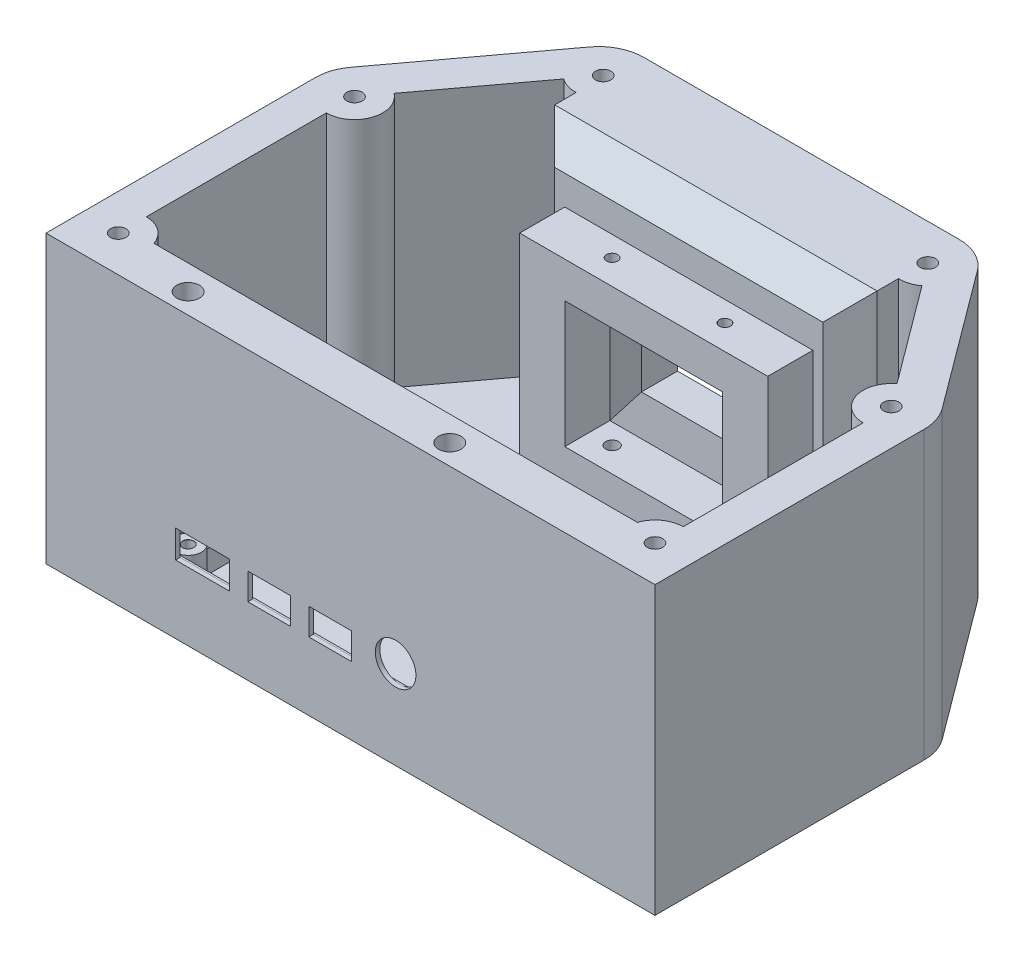
SolidWorks part; units mm, degrees
ref_plane "Front Plane" through (0, 0, 0) normal (0, 0, 1) x (1, 0, 0)
ref_plane "Top Plane" through (0, 0, 0) normal (0, 1, 0) x (1, 0, 0)
ref_plane "Right Plane" through (0, 0, 0) normal (1, 0, 0) x (0, 0, -1)
sketch "Sketch1" plane through (0, 0, 0) normal (0, 1, 0) x (1, 0, 0)
  line L0 (-112.8099, -62.3676) -> (-112.8099, -13.3676) construction
  line L1 (-112.8099, -13.3676) -> (-54.8099, -13.3676) construction
  line L2 (-54.8099, -13.3676) -> (-54.8099, -62.3676) construction
  line L3 (-54.8099, -62.3676) -> (-112.8099, -62.3676) construction
  line L4 (-139.8099, -3.8676) -> (-112.3099, 33.1324)
  line L5 (-139.8099, -66.8676) -> (-4.8099, -66.8676)
  line L8 (-4.8099, -66.8676) -> (-4.8099, -3.8676)
  line L9 (-72.3099, 46.1894) -> (-72.3099, -66.8676) construction
  line L10 (-4.8099, -3.8676) -> (-32.3099, 33.1324)
  line L11 (-32.3099, 33.1324) -> (-112.3099, 33.1324)
  line L12 (-139.8099, -3.8676) -> (-139.8099, -66.8676)
  dimension "D1" = 49
  dimension "D2" = 58
  dimension "D3" = 135
  dimension "D4" = 100
  dimension "D5" = 50
  dimension "D6" = 4.5
  dimension "D7" = 80
  dimension "D9" = 63
extrude "Boss-Extrude1" add sketch "Sketch1" along normal blind 7
sketch "Sketch2" plane through (0, 7, 0) normal (0, 1, 0) x (1, 0, 0)
  line L0 (-72.3099, 33.1324) -> (-72.3099, -66.8676) construction
  line L1 (-32.3099, 33.1324) -> (-112.3099, 33.1324) construction
  line L2 (-139.8099, -66.8676) -> (-4.8099, -66.8676) construction
  line L3 (-4.8099, -66.8676) -> (-4.8099, -3.8676) construction
  line L5 (-112.8099, -13.3676) -> (-54.8099, -13.3676) construction
  line L6 (-54.8099, -62.3676) -> (-112.8099, -62.3676) construction
  line L7 (-112.8099, -62.3676) -> (-112.8099, -13.3676) construction
  line L8 (-54.8099, -13.3676) -> (-54.8099, -62.3676) construction
  line L9 (-83.8099, -62.3676) -> (-83.8099, -13.3676) construction
  line L10 (-112.8099, -37.8676) -> (-54.8099, -37.8676) construction
  line L11 (-112.8099, -65.3676) -> (-54.8099, -65.3676)
  line L12 (-115.8099, -62.3676) -> (-115.8099, -13.3676)
  line L13 (-112.8099, -10.3676) -> (-54.8099, -10.3676)
  line L14 (-51.8099, -13.3676) -> (-51.8099, -62.3676)
  line L15 (-112.8099, -16.3676) -> (-112.8099, -59.3676)
  line L16 (-109.8099, -62.3676) -> (-57.8099, -62.3676)
  line L17 (-54.8099, -16.3676) -> (-54.8099, -59.3676)
  line L18 (-109.8099, -13.3676) -> (-57.8099, -13.3676)
  line L22 (-99.8099, -1.8676) -> (-44.8099, -1.8676)
  line L23 (-99.8099, -1.8676) -> (-99.8099, 8.1324)
  line L24 (-99.8099, 8.1324) -> (-44.8099, 8.1324)
  line L25 (-44.8099, -1.8676) -> (-44.8099, 8.1324)
  line L26 (-99.8099, -1.8676) -> (-44.8099, 8.1324) construction
  line L27 (-99.8099, 8.1324) -> (-44.8099, -1.8676) construction
  circle A0 centre (-112.8099, -13.3676) radius 3
  circle A1 centre (-112.8099, -62.3676) radius 3
  circle A2 centre (-54.8099, -62.3676) radius 3
  circle A3 centre (-54.8099, -13.3676) radius 3
  point P42 (-72.3099, 3.1324)
  dimension "D6" = 6
  dimension "D1" = 55
  dimension "D2" = 50
  dimension "D3" = 4.5
  dimension "D4" = 58
  dimension "D5" = 49
  dimension "D7" = 10
  dimension "D8" = 35
extrude "Boss-Extrude2" add sketch "Sketch2" along normal blind 5 contours L12 A1 L15 A0 | L18 A3 L13 A0 | A2 L16 A1 L11 | L14 A3 L17 A2 region at (-83.8099, 7, 63.8877) region at (-114.334, 7, 37.8676) region at (-53.2858, 7, 37.8676) region at (-83.8099, 7, 11.8476)
extrude "Boss-Extrude3" add sketch "Sketch2<3>" along normal blind 8 contours A0 | A3 | A2 | A1 region at (-112.8099, 7, 62.3676) region at (-54.8099, 7, 62.3676) region at (-112.8099, 7, 13.3676) region at (-54.8099, 7, 13.3676)
sketch "Sketch2<3>" plane through (0, 7, 0) normal (0, 1, 0) x (1, 0, 0) same geometry as "Sketch2"
hole_wizard "Ø2.5mm Dowel Hole1" positions "Sketch4" profile "Sketch6" hole size "Ø2.5" standard "ANSI Metric"
sketch "Sketch4" plane through (0, 15, 0) normal (0, 1, 0) x (1, 0, 0)
  point P0 (-54.8099, -13.3676)
  point P3 (-112.8099, -13.3676)
  point P6 (-54.8099, -62.3676)
  point P12 (-112.8099, -62.3676)
sketch "Sketch6" plane through (-54.8099, 15, 13.3676) normal (1, 0, 0) x (0, 0, 1)
  line L0 (0, 0) -> (0, 8.7511)
  line L1 (0, 8.7511) -> (1.25, 8)
  line L2 (1.25, 8) -> (1.25, 0.025)
  line L3 (1.25, 0.025) -> (1.275, 0)
  line L5 (1.275, 0) -> (0, 0)
  line L6 (-1.25, 0.025) -> (-1.275, 0) construction
  line L10 (0, 8.7511) -> (-1.25, 8) construction
  line L11 (0, -6.35) -> (0, 107.95) construction
  dimension "Hole Dia." = 2.5
  dimension "Hole Depth" = 8
  dimension "Near C'Sink Dia." = 2.55
  dimension "Near C'Sink Angle" = 90
  dimension "Drill Angle" = 118
extrude "Boss-Extrude4" add sketch "Sketch2<4>" along normal blind 8 contours L22 L25 L24 L23 region at (-72.3099, 7, -3.1324)
sketch "Sketch2<4>" plane through (0, 7, 0) normal (0, 1, 0) x (1, 0, 0) same geometry as "Sketch2"
sketch "Sketch7" plane through (0, 15, 0) normal (0, 1, 0) x (1, 0, 0)
  line L0 (-99.8099, -1.8676) -> (-44.8099, -1.8676) construction
  line L1 (-99.8099, 8.1324) -> (-89.8099, 8.1324)
  line L2 (-99.8099, 8.1324) -> (-99.8099, -1.8676)
  line L3 (-99.8099, -1.8676) -> (-89.8099, -1.8676)
  line L4 (-89.8099, 8.1324) -> (-89.8099, -1.8676)
  line L5 (-72.3099, 8.1324) -> (-72.3099, -1.8676) construction
  line L10 (-99.8099, 8.1324) -> (-44.8099, 8.1324) construction
  line L11 (-44.8099, -1.8676) -> (-54.8099, -1.8676)
  line L12 (-54.8099, 8.1324) -> (-54.8099, -1.8676)
  line L13 (-44.8099, 8.1324) -> (-54.8099, 8.1324)
  line L14 (-44.8099, 8.1324) -> (-44.8099, -1.8676)
  dimension "D1" = 10
extrude "Boss-Extrude5" add sketch "Sketch7" along normal blind 28
sketch "Sketch9" plane through (0, 43, 0) normal (0, 1, 0) x (1, 0, 0)
  line L1 (-99.8099, 8.1324) -> (-44.8099, 8.1324)
  line L2 (-99.8099, 8.1324) -> (-99.8099, -1.8676)
  line L3 (-99.8099, -1.8676) -> (-44.8099, -1.8676)
  line L4 (-44.8099, 8.1324) -> (-44.8099, -1.8676)
extrude "Boss-Extrude6" add sketch "Sketch9" along normal blind 8
sketch "Sketch10" plane through (0, 0, -33.1324) normal (0, 0, -1) x (-1, 0, 0)
  line L0 (72.3099, 7) -> (72.3099, 51) construction
  line L1 (32.3099, 7) -> (44.8099, 7)
  line L2 (32.3099, 7) -> (32.3099, 51)
  line L3 (32.3099, 51) -> (44.8099, 51)
  line L4 (44.8099, 7) -> (44.8099, 51)
  line L5 (32.3099, 7) -> (112.3099, 7) construction
  line L6 (44.8099, 51) -> (99.8099, 51) construction
  line L7 (112.3099, 51) -> (99.8099, 51)
  line L8 (99.8099, 7) -> (99.8099, 51)
  line L9 (112.3099, 7) -> (99.8099, 7)
  line L10 (112.3099, 7) -> (112.3099, 51)
  line L11 (44.8099, 7) -> (99.8099, 7)
  line L12 (32.3099, 51) -> (112.3099, 51)
  line L13 (32.3099, 51) -> (32.3099, 63.5)
  line L14 (32.3099, 63.5) -> (112.3099, 63.5)
  line L15 (112.3099, 51) -> (112.3099, 63.5)
  line L16 (44.8099, 51) -> (99.8099, 51)
  line L17 (44.8099, 51) -> (99.8099, 51)
  line M16 (112.3099, 7) -> (32.3099, 7)
  dimension "D1" = 12.5
extrude "Boss-Extrude7" add sketch "Sketch10" against normal blind 8 contours L4 L3 L2 M16 | L7 L15 L14 L13 L3 L12 L17 | L10 L7 L8 M16 region at (-38.5599, 29, -33.1324) region at (-72.3099, 57.25, -33.1324) region at (-106.0599, 29, -33.1324)
sketch "Sketch11" plane through (0, 7, 0) normal (0, 1, 0) x (1, 0, 0)
  line L0 (-44.8099, 25.1324) -> (-99.8099, 25.1324)
  line L1 (-131.8099, -66.8676) -> (-131.8099, -6.515)
  line L2 (-139.8099, -66.8676) -> (-4.8099, -66.8676) construction
  line L3 (-131.8099, -6.515) -> (-108.2882, 25.1324)
  line L9 (-32.3099, 25.1324) -> (-112.3099, 25.1324) construction
  line L13 (-32.3099, 33.1324) -> (-112.3099, 33.1324) construction
  line L15 (-112.3099, 33.1324) -> (-139.8099, -3.8676) construction
  line L16 (-108.2882, 25.1324) -> (-108.2882, 33.1324)
  line L17 (-108.2882, 33.1324) -> (-112.3099, 33.1324)
  line L18 (-112.3099, 33.1324) -> (-139.8099, -3.8676)
  line L19 (-139.8099, -3.8676) -> (-139.8099, -66.8676)
  line L20 (-139.8099, -66.8676) -> (-131.8099, -66.8676)
  line L21 (-72.3099, 33.1324) -> (-72.3099, -66.8676) construction
  line L22 (-4.8099, -66.8676) -> (-12.8099, -66.8676)
  line L23 (-4.8099, -3.8676) -> (-4.8099, -66.8676)
  line L24 (-32.3099, 33.1324) -> (-4.8099, -3.8676)
  line L25 (-36.3316, 33.1324) -> (-32.3099, 33.1324)
  line L26 (-36.3316, 25.1324) -> (-36.3316, 33.1324)
  line L27 (-12.8099, -6.515) -> (-36.3316, 25.1324)
  line L28 (-12.8099, -66.8676) -> (-12.8099, -6.515)
  line L29 (-51.8099, -58.8676) -> (-12.8099, -58.8676)
  line L30 (-51.8099, -13.3676) -> (-51.8099, -62.3676) construction
  line L31 (-115.8099, -58.8676) -> (-131.8099, -58.8676)
  line L32 (-115.8099, -62.3676) -> (-115.8099, -13.3676) construction
  line L33 (-131.8099, -65.3676) -> (-12.8099, -65.3676)
  line M19 (-99.8099, 25.1324) -> (-112.3099, 25.1324)
  line M20 (-112.3099, 25.1324) -> (-112.3099, 33.1324)
  line M21 (-112.3099, 33.1324) -> (-139.8099, -3.8676)
  line M22 (-139.8099, -3.8676) -> (-139.8099, -66.8676)
  line M23 (-139.8099, -66.8676) -> (-4.8099, -66.8676)
  dimension "D1" = 8
  dimension "D2" = 8
  dimension "D3" = 8
  dimension "D4" = 8
  dimension "D5" = 8
  dimension "D6" = 8
  dimension "D7" = 119
  dimension "D8" = 16
  dimension "D9" = 1.5
extrude "Boss-Extrude10" add sketch "Sketch11" along normal blind 56.5 contours L1 L3 M19 M20 M21 M22 M23 | L22 L28 L27 L26 L25 L24 L23 region at (-135.8099, 7, 65.8191)
fillet "Fillet8" radius 10 4 edges at (-139.8099, 31.75, 3.8676) (-112.3099, 31.75, -33.1324) (-4.8099, 31.75, 3.8676) (-32.3099, 31.75, -33.1324)
sketch "Sketch16" plane through (0, 0, 66.8676) normal (0, 0, 1) x (1, 0, 0)
  line L0 (-73.5599, 19.04) -> (-73.5599, 17.7198) construction
  line L1 (-111.0799, 21.25) -> (-99.1399, 21.25)
  line L2 (-111.0799, 21.25) -> (-111.0799, 15.09)
  line L3 (-111.0799, 15.09) -> (-99.1399, 15.09)
  line L4 (-99.1399, 21.25) -> (-99.1399, 15.09)
  line L5 (-95.0599, 20.99) -> (-85.5599, 20.99)
  line L6 (-95.0599, 20.99) -> (-95.0599, 15.09)
  line L7 (-95.0599, 15.09) -> (-85.5599, 15.09)
  line L8 (-85.5599, 20.99) -> (-85.5599, 15.09)
  line L9 (-81.5599, 20.99) -> (-72.0599, 20.99)
  line L10 (-81.5599, 20.99) -> (-81.5599, 15.09)
  line L11 (-81.5599, 15.09) -> (-72.0599, 15.09)
  line L12 (-72.0599, 20.99) -> (-72.0599, 15.09)
  line L13 (-80.0599, 17.7198) -> (-80.0599, 19.04) construction
  line L14 (-76.9699, 16.59) -> (-78.9654, 16.59) construction
  line L15 (-79.6099, 19.49) -> (-74.0099, 19.49) construction
  line L16 (-93.1099, 19.49) -> (-87.5099, 19.49) construction
  line L17 (-90.4699, 16.59) -> (-92.4654, 16.59) construction
  line L18 (-93.5599, 17.7198) -> (-93.5599, 19.04) construction
  line L19 (-87.0599, 19.04) -> (-87.0599, 17.7198) construction
  line L20 (-108.2799, 19.75) -> (-101.9399, 19.75) construction
  line L21 (-108.2799, 16.59) -> (-101.9399, 16.59) construction
  line L22 (-109.5799, 17.89) -> (-109.5799, 18.45) construction
  line L23 (-100.6399, 17.89) -> (-100.6399, 18.45) construction
  circle A0 centre (-62.3099, 19.59) radius 4.5
  circle A1 centre (-62.3099, 19.59) radius 3 construction
  dimension "D1" = 1.5
  dimension "D2" = 1.5
  dimension "D3" = 1.5
  dimension "D4" = 1.5
  dimension "D5" = 1.5
  dimension "D6" = 1.5
  dimension "D7" = 1.5
  dimension "D8" = 1.5
  dimension "D9" = 1.5
  dimension "D10" = 1.5
  dimension "D11" = 1.5
  dimension "D12" = 1.5
  dimension "D13" = 1.5
hole_wizard "Ø2.5mm Dowel Hole2" positions "Sketch18" profile "Sketch19" hole size "Ø2.5" standard "ANSI Metric" end condition up to next
sketch "Sketch18" plane through (0, 51, 0) normal (0, 1, 0) x (1, 0, 0)
  point P0 (-84.8099, 3.6324)
  point P3 (-59.8099, 3.6324)
sketch "Sketch19" plane through (-84.8099, 51, -3.6324) normal (1, 0, 0) x (0, 0, 1)
  line L0 (0, 0) -> (0, 8)
  line L1 (0, 8) -> (1.25, 8)
  line L2 (1.25, 8) -> (1.25, 0)
  line L5 (1.25, 0) -> (0, 0)
  line L11 (0, -6.35) -> (0, 107.95) construction
  dimension "Thru Hole Dia." = 2.5
  dimension "Thru Hole Depth" = 8
hole_wizard "CBORE for M2.5 Hex Head Machine Screw1" positions "Sketch20" profile "Sketch23" counterbore size "M2.5" standard "ANSI Metric" end condition up to next
sketch "Sketch20" plane through (0, 0, 0) normal (0, -1, 0) x (-1, 0, 0)
  point P0 (59.8099, 3.6324)
  point P3 (84.8099, 3.6324)
sketch "Sketch23" plane through (-59.8099, 0, -3.6324) normal (1, 0, 0) x (0, 0, -1)
  line L0 (0, 0) -> (0, 15)
  line L1 (0, 15) -> (1.45, 15)
  line L3 (1.45, 15) -> (1.45, 12)
  line L4 (1.45, 12) -> (3.64, 12)
  line L5 (3.64, 12) -> (3.64, 0)
  line L7 (3.64, 0) -> (0, 0)
  line L11 (0, -6.35) -> (0, 107.95) construction
  dimension "Thru Hole Dia." = 2.9
  dimension "Thru Hole Depth" = 15
  dimension "C'Bore Dia." = 7.28
  dimension "C'Bore Depth" = 12
sketch "Sketch26" plane through (0, 7, 0) normal (0, 1, 0) x (1, 0, 0)
  line L0 (-115.8099, -58.8676) -> (-131.8099, -58.8676)
  line L1 (-115.8099, -62.3676) -> (-115.8099, -13.3676) construction
  line L2 (-131.8099, -66.8676) -> (-131.8099, -6.515) construction
  line L3 (-131.8099, -66.8676) -> (-12.8099, -66.8676) construction
  line L4 (-51.8099, -58.8676) -> (-12.8099, -58.8676)
  line L5 (-51.8099, -13.3676) -> (-51.8099, -62.3676) construction
  line L6 (-12.8099, -66.8676) -> (-12.8099, -6.515) construction
  line L7 (-12.8099, -58.8676) -> (-12.8099, -66.8676)
  line L8 (-12.8099, -66.8676) -> (-131.8099, -66.8676)
  line L9 (-131.8099, -66.8676) -> (-131.8099, -58.8676)
  line L11 (-51.8099, -58.8676) -> (-51.8099, -62.3676)
  line L12 (-51.8099, -62.3676) -> (-54.8099, -65.3676)
  line L13 (-54.8099, -65.3676) -> (-112.8099, -65.3676)
  line L14 (-112.8099, -65.3676) -> (-115.8099, -62.3676)
  line L15 (-115.8099, -62.3676) -> (-115.8099, -58.8676)
  circle A2 centre (-112.8099, -62.3676) radius 3 construction
  dimension "D1" = 8
extrude "Boss-Extrude11" add sketch "Sketch26" along normal up to surface (8 mm away) up to face at (-112.8099, 15, 63.6426)
sketch "Sketch27" plane through (0, 15, 0) normal (0, 1, 0) x (1, 0, 0)
  line L0 (-118.3099, -58.8676) -> (-118.3099, -65.8676)
  line L1 (-115.8099, -58.8676) -> (-131.8099, -58.8676) construction
  line L2 (-118.3099, -65.8676) -> (-12.8099, -65.8676)
  line L3 (-12.8099, -66.8676) -> (-12.8099, -58.8676) construction
  line L4 (-116.3099, -12.8676) -> (-116.3099, -62.8676) construction
  line L5 (-131.8099, -66.8676) -> (-12.8099, -66.8676) construction
  line L14 (-54.8099, -65.3676) -> (-112.8099, -65.3676)
  line L15 (-115.8099, -62.3676) -> (-115.8099, -58.8676)
  line L16 (-115.8099, -58.8676) -> (-131.8099, -58.8676)
  line L17 (-131.8099, -58.8676) -> (-131.8099, -66.8676)
  line L18 (-131.8099, -66.8676) -> (-12.8099, -66.8676)
  line L19 (-12.8099, -66.8676) -> (-12.8099, -58.8676)
  line L20 (-12.8099, -58.8676) -> (-51.8099, -58.8676)
  line L21 (-51.8099, -58.8676) -> (-51.8099, -62.3676)
  line L24 (-118.3099, -58.8676) -> (-131.8099, -58.8676)
  line L25 (-131.8099, -58.8676) -> (-131.8099, -66.8676)
  line L26 (-131.8099, -66.8676) -> (-12.8099, -66.8676)
  line L27 (-12.8099, -66.8676) -> (-12.8099, -65.8676)
  arc A2 (-51.8099, -62.3676) -> (-54.8099, -65.3676) centre (-54.8099, -62.3676) ccw
  arc A3 (-112.8099, -65.3676) -> (-115.8099, -62.3676) centre (-112.8099, -62.3676) ccw
  dimension "D1" = 2
  dimension "D2" = 1
  dimension "D3" = 0
extrude "Boss-Extrude12" add sketch "Sketch27" along normal blind 20 contours L24 L25 L26 L27 L2 L0
sketch "Sketch28" plane through (0, 35, 0) normal (0, 1, 0) x (1, 0, 0)
  line L6 (-12.8099, -66.8676) -> (-12.8099, -6.515) construction
  line L7 (-131.8099, -66.8676) -> (-12.8099, -66.8676)
  line L8 (-131.8099, -66.8676) -> (-131.8099, -56.8676)
  line L9 (-131.8099, -56.8676) -> (-12.8099, -56.8676)
  line L10 (-12.8099, -66.8676) -> (-12.8099, -56.8676)
  dimension "D1" = 10
extrude "Boss-Extrude13" add sketch "Sketch28" along normal up to surface (28.5 mm away) up to face at (-72.3099, 63.5, 7.5207)
extrude "Cut-Extrude1" cut sketch "Sketch16" against normal up to next
chamfer "Chamfer1" distance 9 angle 45 1 edges at (-72.3099, 35, 56.8676)
sketch "Sketch29" plane through (0, 63.5, 0) normal (0, 1, 0) x (1, 0, 0)
  circle A0 centre (-112.8099, -62.3676) radius 2.5
  circle A1 centre (-54.8099, -62.3676) radius 2.5
  dimension "D1" = 5
  dimension "D2" = 5
extrude "Cut-Extrude2" cut sketch "Sketch29" against normal up to next
sketch "Sketch30" plane through (0, 0, 0) normal (0, -1, 0) x (1, 0, 0)
  line L0 (-139.8099, 7.1769) -> (-139.8099, 66.8676) construction
  line L1 (-139.8099, 66.8676) -> (-4.8099, 66.8676) construction
  line L2 (-115.3087, -29.0976) -> (-137.8358, 1.2116) construction
  line L3 (-72.3099, -33.1324) -> (-72.3099, 66.8676) construction
  line L4 (-37.337, -33.1324) -> (-107.2827, -33.1324) construction
  circle A0 centre (-131.8099, 58.8676) radius 4.25
  circle A1 centre (-131.8099, 6.4735) radius 4.25
  circle A2 centre (-108.2882, -25.1324) radius 4.25
  circle A4 centre (-131.8099, 58.8676) radius 6.25
  circle A5 centre (-131.8099, 6.4735) radius 6.25
  circle A6 centre (-108.2882, -25.1324) radius 6.25
  circle A7 centre (-36.3316, -25.1324) radius 6.25
  circle A8 centre (-12.8099, 6.4735) radius 6.25
  circle A9 centre (-12.8099, 58.8676) radius 6.25
  circle A10 centre (-36.3316, -25.1324) radius 4.25
  circle A11 centre (-12.8099, 6.4735) radius 4.25
  circle A12 centre (-12.8099, 58.8676) radius 4.25
  dimension "D1" = 8
  dimension "D3" = 8
  dimension "D7" = 8.5
  dimension "D8" = 8.5
  dimension "D9" = 8.5
  dimension "D2" = 8
  dimension "D4" = 8
  dimension "D5" = 8
  dimension "D6" = 8
  dimension "D10" = 2
extrude "Boss-Extrude16" add sketch "Sketch30" against normal up to surface (63.5 mm away) contours A0 | A4 A0 | A5 A1 | A1 | A6 A2 | A2 | A12 | A9 A12 | A8 A11 | A11 | A7 A10 | A10 region at (-131.8099, 0, 58.8676) region at (-131.8099, 0, 6.4735) region at (-108.2882, 0, -25.1324) region at (-137.8831, 0, 58.8676) region at (-137.8831, 0, 6.4735) region at (-114.3614, 0, -25.1324) region at (-42.4048, 0, -25.1324) region at (-18.8831, 0, 6.4735) region at (-18.8831, 0, 58.8676) region at (-36.3316, 0, -25.1324) region at (-12.8099, 0, 6.4735) region at (-12.8099, 0, 58.8676) up to face at (-112.8099, 63.5, 64.8676)
sketch "Sketch45" plane through (0, 0, -8.1324) normal (0, 0, -1) x (-1, 0, 0)
  line L5 (44.8099, 51) -> (99.8099, 51)
  line L6 (44.8099, 51) -> (44.8099, 7)
  line L7 (44.8099, 7) -> (99.8099, 7)
  line L8 (99.8099, 51) -> (99.8099, 7)
  point P0 (0, 0)
sketch "Sketch50" plane through (0, 0, -25.1324) normal (0, 0, 1) x (1, 0, 0)
  line L0 (-102.0382, 63.5) -> (-108.0382, 63.5)
  line L1 (-99.8099, 51) -> (-44.8099, 51)
  line L2 (-99.8099, 51) -> (-99.8099, 7)
  line L3 (-99.8099, 7) -> (-44.8099, 7)
  line L4 (-44.8099, 51) -> (-44.8099, 7)
  line L5 (-102.0382, 63.5) -> (-42.5816, 63.5)
  line L6 (-102.0382, 63.5) -> (-102.0382, 7)
  line L7 (-102.0382, 7) -> (-42.5816, 7)
  line L8 (-42.5816, 63.5) -> (-42.5816, 7)
  line L9 (-108.0382, 63.5) -> (-108.0382, 7)
  line L10 (-108.0382, 7) -> (-99.8099, 7)
  line L11 (-42.5816, 63.5) -> (-36.5816, 63.5)
  line L12 (-36.5816, 63.5) -> (-36.5816, 7)
  line L13 (-36.5816, 7) -> (-42.5816, 7)
  line L15 (-108.0382, 63.5) -> (-36.5816, 63.5)
  line L16 (-108.0382, 63.5) -> (-108.0382, 7)
  line L17 (-108.0382, 7) -> (-36.5816, 7)
  line L18 (-36.5816, 63.5) -> (-36.5816, 7)
  line M11 (-42.5816, 7) -> (-42.5816, 63.5)
  line M12 (-42.5816, 63.5) -> (-102.0382, 63.5)
  line M13 (-102.0382, 63.5) -> (-102.0382, 7)
  line M14 (-102.0382, 7) -> (-99.8099, 7)
  line M15 (-99.8099, 7) -> (-99.8099, 51)
  line M16 (-99.8099, 51) -> (-44.8099, 51)
  line M17 (-44.8099, 51) -> (-44.8099, 7)
  line M18 (-44.8099, 7) -> (-42.5816, 7)
  dimension "D1" = 6
  dimension "D2" = 6
extrude "Boss-Extrude32" add sketch "Sketch50" along normal up to vertex (17 mm away) contours L9 L10 L0 M13 | M18 M11 M12 M13 M14 M15 M16 M17 | L13 L12 L11 M11 | L3 M15 M17 M16 region at (-105.0382, 35.25, -25.1324) region at (-72.3099, 51.3525, -25.1324) region at (-39.5816, 35.25, -25.1324) region at (-72.3099, 29, -25.1324) up to point (-99.8099, 51, -8.1324)
extrude "Cut-Extrude3" cut sketch "Sketch30<6>" against normal offset from surface (57.5 mm away) 6 contours A12 | A0 | A1 | A2 | A11 | A10 region at (-131.8099, 0, 58.8676) region at (-131.8099, 0, 6.4735) region at (-108.2882, 0, -25.1324) region at (-36.3316, 0, -25.1324) region at (-12.8099, 0, 6.4735) region at (-12.8099, 0, 58.8676) up to face at (-72.3099, 63.5, 11.0406)
sketch "Sketch30<6>" plane through (0, 0, 0) normal (0, -1, 0) x (1, 0, 0) same geometry as "Sketch30"
hole_wizard "CBORE for M3 Hex Head Machine Screw1" positions "Sketch33" profile "Sketch32" counterbore size "M3" standard "ANSI Metric" end condition through all
sketch "Sketch33" plane through (0, 57.5, 0) normal (0, -1, 0) x (-1, 0, 0)
  point P0 (12.8099, -58.8676)
  point P3 (12.8099, -6.4735)
  point P6 (36.3316, 25.1324)
  point P9 (131.8099, -58.8676)
  point P12 (131.8099, -6.4735)
  point P15 (108.2882, 25.1324)
sketch "Sketch32" plane through (-12.8099, 57.5, 58.8676) normal (1, 0, 0) x (0, 0, -1)
  line L0 (0, 0) -> (0, 6)
  line L1 (0, 6) -> (1.7, 6)
  line L3 (1.7, 6) -> (1.7, 2.3)
  line L4 (1.7, 2.3) -> (4.2, 2.3)
  line L5 (4.2, 2.3) -> (4.2, 0)
  line L7 (4.2, 0) -> (0, 0)
  line L11 (0, -6.35) -> (0, 107.95) construction
  dimension "Thru Hole Dia." = 3.4
  dimension "Thru Hole Depth" = 6
  dimension "C'Bore Dia." = 8.4
  dimension "C'Bore Depth" = 2.3
ref_plane "Plane4" through (0, 0, -18.8874) normal (0, 0, 1) x (1, 0, 0)
chamfer "Chamfer5" distance 6 angle 45 3 edges at (-108.0382, 35.25, -8.1324) (-72.3099, 63.5, -8.1324) (-36.5816, 35.25, -8.1324)
sketch "Sketch58" plane through (0, 0, -25.1324) normal (0, 0, -1) x (-1, 0, 0)
  line L1 (44.8099, 51) -> (99.8099, 51)
  line L2 (44.8099, 51) -> (44.8099, 7)
  line L3 (44.8099, 7) -> (99.8099, 7)
  line L4 (99.8099, 51) -> (99.8099, 7)
sketch "Sketch59" plane through (0, 0, -8.1324) normal (0, 0, 1) x (1, 0, 0)
  line L1 (-54.8099, 15) -> (-89.8099, 15)
  line L2 (-54.8099, 15) -> (-54.8099, 43)
  line L3 (-54.8099, 43) -> (-89.8099, 43)
  line L4 (-89.8099, 15) -> (-89.8099, 43)
loft "Cut-Loft20" cut profiles "Sketch58", "Sketch59"
